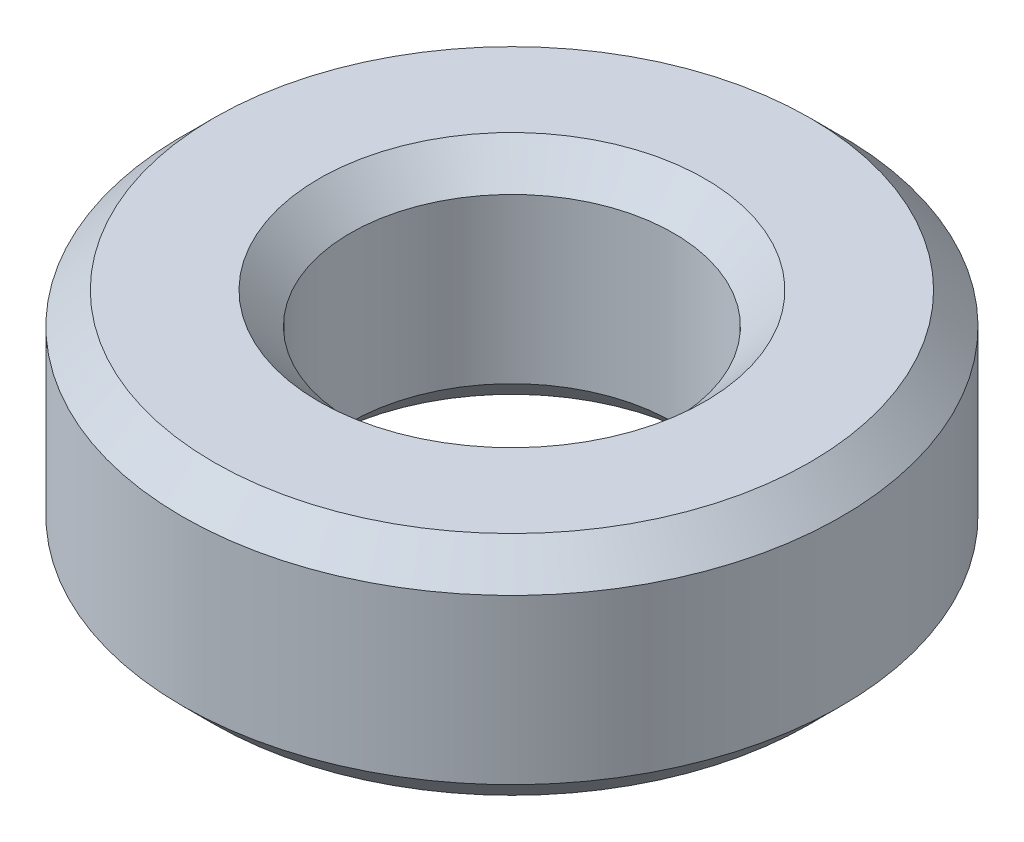
SolidWorks part; units mm, degrees
ref_plane "Front Plane" through (0, 0, 0) normal (0, 0, 1) x (1, 0, 0)
ref_plane "Top Plane" through (0, 0, 0) normal (0, 1, 0) x (1, 0, 0)
ref_plane "Right Plane" through (0, 0, 0) normal (1, 0, 0) x (0, 0, -1)
sketch "Sketch1" plane through (0, 0, 0) normal (0, 1, 0) x (1, 0, 0)
  circle A0 centre (0, 0) radius 30
  dimension "SLEEVE_OD" = 60
extrude "Boss-Extrude1" add sketch "Sketch1" along normal blind 20.6379
sketch "Sketch2" plane through (0, 0, 0) normal (0, 1, 0) x (1, 0, 0)
  circle A0 centre (0, 0) radius 14.7109
  dimension "BORE_D" = 29.4217
extrude "Cut-Extrude1" cut sketch "Sketch2" along normal through all
chamfer "Chamfer1" distance 2.8593 angle 45 4 edges at (0, 20.6379, 14.7109) (0, 0, 14.7109) (0, 0, 30) (0, 20.6379, 30)
